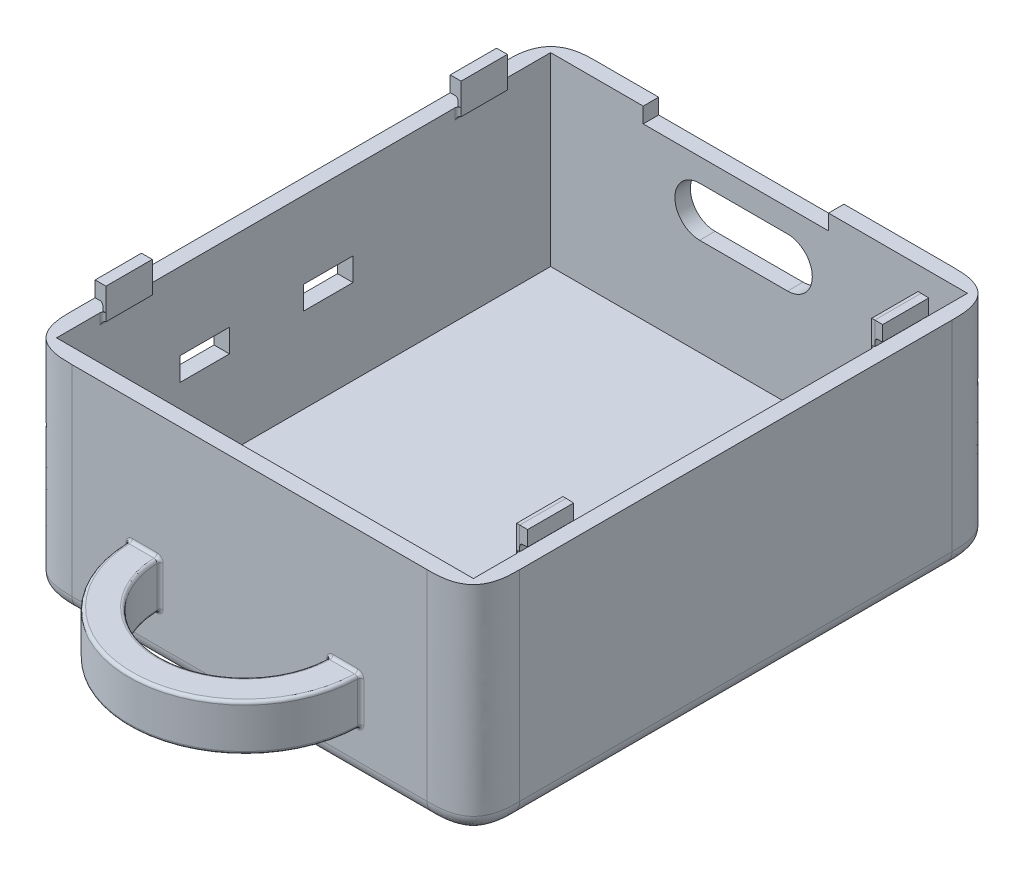
SolidWorks part; units mm, degrees
ref_plane "Front Plane" through (0, 0, 0) normal (0, 0, 1) x (1, 0, 0)
ref_plane "Top Plane" through (0, 0, 0) normal (0, 1, 0) x (1, 0, 0)
ref_plane "Right Plane" through (0, 0, 0) normal (1, 0, 0) x (0, 0, -1)
sketch "Sketch1" plane through (0, 0, 0) normal (0, 1, 0) x (1, 0, 0)
  line L1 (-148.5843, 96.7753) -> (-119.5843, 96.7753)
  line L2 (-148.5843, 96.7753) -> (-148.5843, 62.7753)
  line L3 (-148.5843, 62.7753) -> (-119.5843, 62.7753)
  line L4 (-119.5843, 96.7753) -> (-119.5843, 62.7753)
  dimension "D1" = 29
  dimension "D2" = 34
extrude "Bottom-Extrude" add sketch "Sketch1" along normal blind 14
fillet "Sid_Corner-Fillet" radius 3 4 edges at (-119.5843, 7, -62.7753) (-148.5843, 7, -62.7753) (-119.5843, 7, -96.7753) (-148.5843, 7, -96.7753) curvature continuous yes
fillet "Bottom-Fillet" radius 1 8 edges
sketch "Sketch2" plane through (0, 14, 0) normal (0, 1, 0) x (1, 0, 0)
  line L0 (-122.5843, 96.7753) -> (-145.5843, 96.7753) construction
  line L1 (-147.5843, 95.7753) -> (-120.5843, 95.7753)
  line L2 (-147.5843, 95.7753) -> (-147.5843, 63.7753)
  line L3 (-147.5843, 63.7753) -> (-120.5843, 63.7753)
  line L4 (-120.5843, 95.7753) -> (-120.5843, 63.7753)
  line L5 (-145.5843, 62.7753) -> (-122.5843, 62.7753) construction
  line L6 (-148.5843, 93.7753) -> (-148.5843, 65.7753) construction
  line L7 (-119.5843, 65.7753) -> (-119.5843, 93.7753) construction
  dimension "D1" = 1
  dimension "D2" = 1
  dimension "D3" = 1
  dimension "D4" = 1
extrude "Cut-Extrude1" cut sketch "Sketch2" against normal blind 12
ref_plane "Plane7" through (0, 0, -62.7753) normal (0, 0, 1) x (1, 0, 0)
ref_plane "Plane8" through (0, 1, 0) normal (0, 1, 0) x (1, 0, 0)
ref_plane "Plane9" through (0, 3, 0) normal (0, -1, 0) x (-1, 0, 0)
sketch "Sketch21" plane through (0, 3, 0) normal (0, -1, 0) x (-1, 0, 0)
  line L0 (-7.8811, 62.7753) -> (7.8811, 62.7753) construction
  line L1 (141.8802, 62.7753) -> (126.8802, 62.7753)
  arc A0 (126.8802, 62.7753) -> (141.8802, 62.7753) centre (134.3802, 62.7753) ccw
  arc A1 (128.8802, 62.7753) -> (139.8802, 62.7753) centre (134.3802, 62.7753) ccw
  dimension "D1" = 15
  dimension "D2" = 2
  dimension "D3" = 5.5
extrude "Boss-Extrude1" add sketch "Sketch21" against normal blind 3 contours A1 L1 A0 region at (-134.3802, 3, -55.443)
fillet "Fillet1" radius 0.2 12 edges at (-139.8802, 4.5, -62.7753) (-128.8802, 4.5, -62.7753) (-127.8802, 6, -62.7753) (-140.8802, 6, -62.7753) (-134.3802, 6, -57.2753) (-141.8802, 4.5, -62.7753) (-134.3802, 6, -55.2753) (-126.8802, 4.5, -62.7753) (-140.8802, 3, -62.7753) (-134.3802, 3, -55.2753) (-127.8802, 3, -62.7753) (-134.3802, 3, -57.2753)
sketch "Sketch22" plane through (0, 0, -96.7753) normal (0, 0, -1) x (-1, 0, 0)
  line L0 (132.2343, 9.9) -> (137.9343, 9.9) construction
  line L1 (132.2343, 11.5) -> (137.9343, 11.5)
  line L2 (132.2343, 8.3) -> (137.9343, 8.3)
  line L3 (122.5843, 14) -> (122.5843, 1) construction
  line L5 (145.5843, 1) -> (145.5843, 14) construction
  line L6 (122.5843, 14) -> (145.5843, 14) construction
  line L8 (129.5843, 14) -> (141.5843, 14)
  line L9 (129.5843, 14) -> (129.5843, 13)
  line L10 (129.5843, 13) -> (141.5843, 13)
  line L11 (141.5843, 14) -> (141.5843, 13)
  arc A0 (132.2343, 11.5) -> (132.2343, 8.3) centre (132.2343, 9.9) ccw
  arc A1 (137.9343, 8.3) -> (137.9343, 11.5) centre (137.9343, 9.9) ccw
  point P2 (135.0843, 9.9)
  dimension "D1" = 5.7
  dimension "D3" = 9.65
  dimension "D4" = 2.5
  dimension "D5" = 7.65
  dimension "D2" = 3.2
  dimension "D6" = 12
  dimension "D7" = 7
  dimension "D8" = 1
  dimension "D9" = 1.5
extrude "Cut-USB" cut sketch "Sketch22" against normal up to next
sketch "Sketch23" plane through (-148.5843, 0, 0) normal (-1, 0, 0) x (0, 0, 1)
  line L0 (-65.7753, 1) -> (-65.7753, 14) construction
  line L1 (-74.9753, 9) -> (-71.7753, 9)
  line L2 (-74.9753, 9) -> (-74.9753, 7.5)
  line L3 (-74.9753, 7.5) -> (-71.7753, 7.5)
  line L4 (-71.7753, 9) -> (-71.7753, 7.5)
  line L5 (-93.7753, 14) -> (-65.7753, 14) construction
  dimension "D1" = 1.5
  dimension "D2" = 3.2
  dimension "D3" = 6
  dimension "D4" = 5
extrude "Cut-BT" cut sketch "Sketch23" against normal up to surface (1 mm away) up to face at (-147.5843, 8, -79.7753)
pattern_linear "LPattern1" count 2 spacing 8 along (0, 0, -1) of "Cut-BT"
sketch "Sketch24" plane through (-120.5843, 0, 0) normal (-1, 0, 0) x (0, 0, 1)
  line L0 (-63.7753, 14) -> (-95.7753, 14) construction
  line L1 (-69.7753, 15.5) -> (-66.7753, 15.5)
  line L2 (-69.7753, 15.5) -> (-69.7753, 13.5)
  line L3 (-69.7753, 13.5) -> (-66.7753, 13.5)
  line L4 (-66.7753, 15.5) -> (-66.7753, 13.5)
  line L5 (-63.7753, 2) -> (-63.7753, 14) construction
  dimension "D1" = 3
  dimension "D2" = 2
  dimension "D3" = 0.5
  dimension "D4" = 3
extrude "Boss-Clip" add sketch "Sketch24" along normal blind 0.2
sketch "Sketch26" plane through (-120.5843, 0, 0) normal (1, 0, 0) x (0, 0, -1)
  line L0 (66.7753, 14) -> (66.7753, 15.5) construction
  line L1 (66.7753, 15.5) -> (69.7753, 15.5)
  line L2 (66.7753, 15.5) -> (66.7753, 14.5)
  line L3 (66.7753, 14.5) -> (69.7753, 14.5)
  line L4 (69.7753, 15.5) -> (69.7753, 14.5)
  line L5 (69.7753, 15.5) -> (69.7753, 14) construction
  line L6 (66.7753, 15.5) -> (69.7753, 15.5) construction
  dimension "D1" = 3
  dimension "D2" = 1
  dimension "D3" = 0
extrude "Boss-ClipExt" add sketch "Sketch26" along normal blind 0.5 draft 1
fillet "Fillet2" radius 0.2 4 edges at (-120.5843, 13.75, -69.7753) (-120.5843, 13.75, -66.7753) (-120.5843, 13.5, -68.2753) (-120.5843, 14.5, -68.2753)
pattern_linear "LPattern2" count 2 spacing 23 along (0, 0, -1) of "Boss-Clip", "Boss-ClipExt", "Fillet2"
sketch "Sketch27" plane through (-147.5843, 0, 0) normal (1, 0, 0) x (0, 0, -1)
  line L0 (95.7753, 14) -> (63.7753, 14) construction
  line L1 (66.7753, 15.5) -> (69.7753, 15.5)
  line L2 (66.7753, 15.5) -> (66.7753, 13.5)
  line L3 (66.7753, 13.5) -> (69.7753, 13.5)
  line L4 (69.7753, 15.5) -> (69.7753, 13.5)
  line L5 (63.7753, 2) -> (63.7753, 14) construction
  dimension "D1" = 3
  dimension "D2" = 2
  dimension "D3" = 0.5
  dimension "D4" = 3
extrude "Boss-Clip1" add sketch "Sketch27" along normal blind 0.2
sketch "Sketch28" plane through (-147.5843, 0, 0) normal (-1, 0, 0) x (0, 0, 1)
  line L0 (-66.7753, 15.5) -> (-66.7753, 14) construction
  line L1 (-69.7753, 15.5) -> (-66.7753, 15.5)
  line L2 (-69.7753, 15.5) -> (-69.7753, 14.5)
  line L3 (-69.7753, 14.5) -> (-66.7753, 14.5)
  line L4 (-66.7753, 15.5) -> (-66.7753, 14.5)
  dimension "D1" = 1
  dimension "D2" = 0
extrude "Boss-ClipExt1" add sketch "Sketch28" along normal blind 0.5
fillet "Fillet4" radius 0.2 4 edges at (-147.5843, 14.5, -68.2753) (-147.5843, 13.75, -69.7753) (-147.5843, 13.5, -68.2753) (-147.5843, 13.75, -66.7753)
pattern_linear "LPattern4" count 2 spacing 23 along (0, 0, -1) of "Boss-Clip1", "Boss-ClipExt1", "Fillet4"
